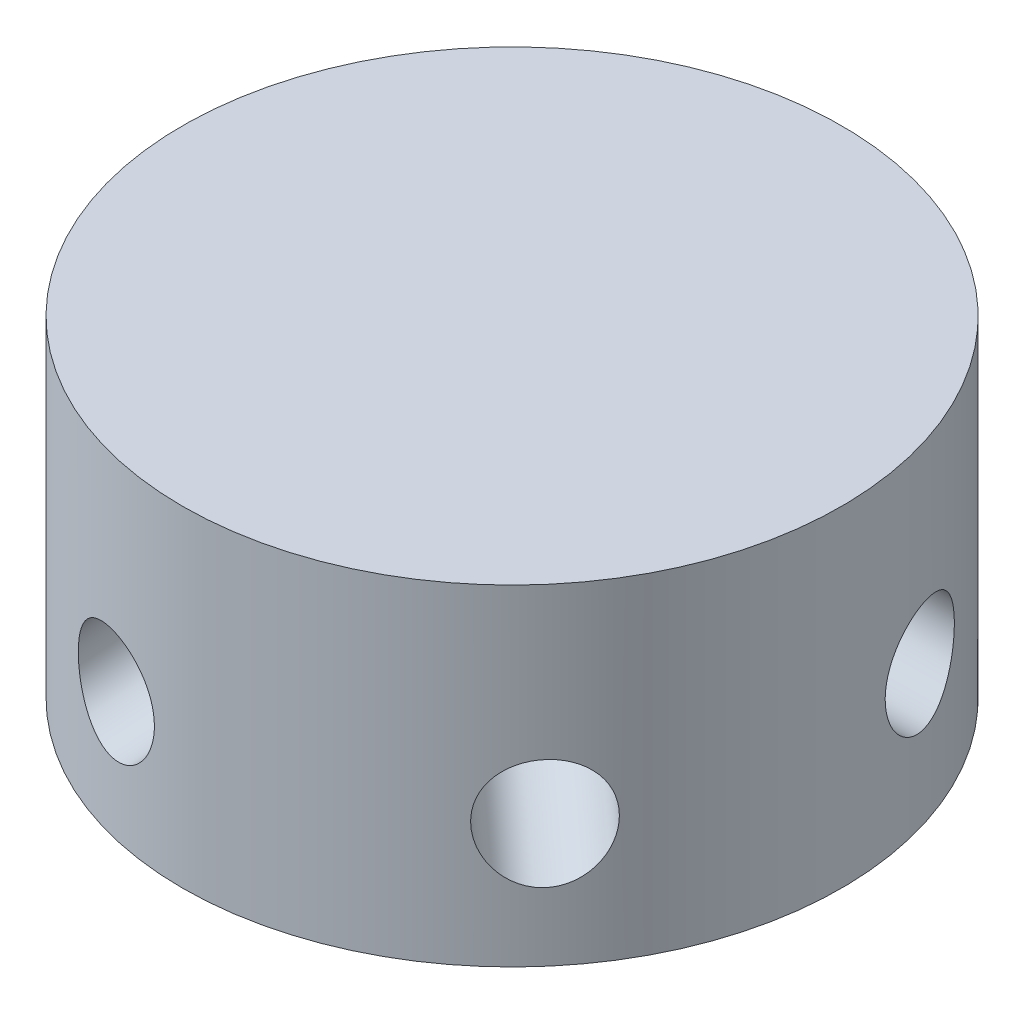
SolidWorks part; units mm, degrees
ref_plane "Front Plane" through (0, 0, 0) normal (0, 0, 1) x (1, 0, 0)
ref_plane "Top Plane" through (0, 0, 0) normal (0, 1, 0) x (1, 0, 0)
ref_plane "Right Plane" through (0, 0, 0) normal (1, 0, 0) x (0, 0, -1)
sketch "Sketch1" plane through (0, 0, 0) normal (0, 1, 0) x (1, 0, 0)
  circle A0 centre (0, 0) radius 10
  dimension "D1" = 20
extrude "base" add sketch "Sketch1" along normal blind 3.0354 and the other way blind 7
ref_axis "6hubaxis" through (0, 5.5, 0) along (0, -1, 0)
ref_plane "Plane1" through (2.6705, -1.0931, 2.7701) normal (-0.6676, 0.2733, -0.6925) x (-0.6559, 0.2243, 0.7208)
sketch "Sketch2" [suppressed] plane through (2.6705, -1.0931, 2.7701) normal (-0.6676, 0.2733, -0.6925) x (-0.6559, 0.2243, 0.7208)
  circle A0 centre (0, 0) radius 1.5 construction
  circle A1 centre (0, 0) radius 1.5
extrude "hole1" [suppressed] cut sketch "Sketch2" against normal through all
pattern_circular "hole1mirror" [suppressed] count 2 over 360 about axis through (0, 5.5, 0) along (0, -1, 0) of bodies 112
ref_plane "Plane2" through (-0.9417, -1.2361, 3.6858) normal (0.2354, 0.309, -0.9215) x (-0.9719, 0.0738, -0.2235)
sketch "Sketch3" plane through (-0.9417, -1.2361, 3.6858) normal (0.2354, 0.309, -0.9215) x (-0.9719, 0.0738, -0.2235)
  circle A0 centre (0, 0) radius 1.5 construction
  circle A1 centre (0, 0) radius 1.5 construction
  circle A2 centre (0, 0) radius 1.6
  dimension "D1" = 3.2
extrude "hole2" cut sketch "Sketch3" against normal through all
pattern_circular "hole2mirror" count 2 over 360 about axis through (0, 5.5, 0) along (0, -1, 0) of "hole2"
ref_plane "Plane3" through (-3.7178, -1.2361, 0.8061) normal (0.9295, 0.309, -0.2015) x (-0.1912, -0.0636, -0.9795)
sketch "Sketch4" plane through (-3.7178, -1.2361, 0.8061) normal (0.9295, 0.309, -0.2015) x (-0.1912, -0.0636, -0.9795)
  circle A0 centre (0, 0) radius 1.5 construction
  circle A1 centre (0, 0) radius 1.5 construction
  circle A2 centre (0, 0) radius 1.6
  dimension "D1" = 3.2
extrude "hole3" cut sketch "Sketch4" against normal through all
pattern_circular "hole3mirror" [suppressed] count 2 over 360 about axis through (0, 5.5, 0) along (0, -1, 0) of bodies 117
ref_plane "Plane4" through (3.672, -1.0931, -1.1497) normal (-0.918, 0.2733, 0.2874) x (0.2755, -0.082, 0.9578)
sketch "Sketch5" plane through (3.672, -1.0931, -1.1497) normal (-0.918, 0.2733, 0.2874) x (0.2755, -0.082, 0.9578)
  circle A0 centre (0, 0) radius 1.5 construction
  circle A1 centre (0, 0) radius 1.5 construction
  circle A2 centre (0, 0) radius 1.6
  dimension "D1" = 3.2
extrude "Cut-Extrude1" cut sketch "Sketch5" against normal through all
ref_plane "Plane5" through (2.8756, -1.2361, 2.4906) normal (-0.7189, 0.309, -0.6227) x (-0.572, 0.2459, 0.7825)
sketch "Sketch6" plane through (2.8756, -1.2361, 2.4906) normal (-0.7189, 0.309, -0.6227) x (-0.572, 0.2459, 0.7825)
  circle A0 centre (0, 0) radius 1.5 construction
  circle A1 centre (0, 0) radius 1.5 construction
  circle A2 centre (0, 0) radius 1.6
  dimension "D1" = 3.2
extrude "Cut-Extrude2" cut sketch "Sketch6" against normal through all
ref_plane "Plane6" through (-2.6705, -1.0931, -2.7701) normal (0.6676, 0.2733, 0.6925) x (0.7445, -0.2451, -0.621)
sketch "Sketch7" plane through (-2.6705, -1.0931, -2.7701) normal (0.6676, 0.2733, 0.6925) x (0.7445, -0.2451, -0.621)
  circle A0 centre (0, 0) radius 1.5 construction
  circle A1 centre (0, 0) radius 1.5 construction
  circle A2 centre (0, 0) radius 1.6
  dimension "D1" = 3.2
extrude "Cut-Extrude3" cut sketch "Sketch7" against normal through all
sketch "Sketch8" plane through (0, -7, 0) normal (0, -1, 0) x (1, 0, 0)
  circle A0 centre (0, 0) radius 5
extrude "Boss-Extrude1" add sketch "Sketch8" along normal blind 2
